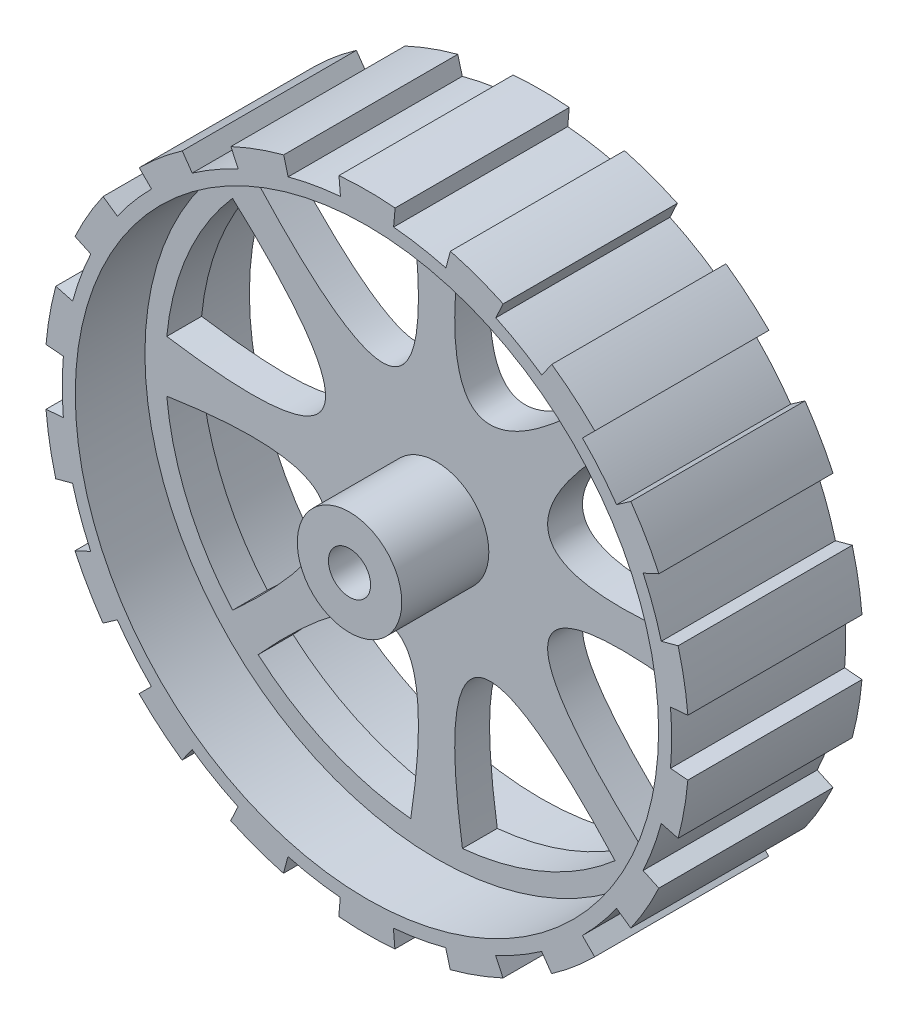
SolidWorks part; units mm, degrees
ref_plane "Front Plane" through (0, 0, 0) normal (0, 0, 1) x (1, 0, 0)
ref_plane "Top Plane" through (0, 0, 0) normal (0, 1, 0) x (1, 0, 0)
ref_plane "Right Plane" through (0, 0, 0) normal (1, 0, 0) x (0, 0, -1)
sketch "Sketch1" plane through (0, 0, 0) normal (0, 0, 1) x (1, 0, 0)
  line L0 (3.2369, 36.8581) -> (3.0619, 34.8658)
  line L1 (-3.2127, 36.8603) -> (-3.039, 34.8678)
  line L2 (15.6479, 33.5283) -> (14.8021, 31.7159)
  line L3 (9.588, 35.7361) -> (9.0698, 33.8044)
  line L4 (26.1715, 26.1544) -> (24.7569, 24.7406)
  line L5 (21.2323, 30.3017) -> (20.0846, 28.6637)
  line L6 (33.5385, 15.6259) -> (31.7256, 14.7812)
  line L7 (30.3156, 21.2124) -> (28.6769, 20.0658)
  line L8 (36.8603, 3.2127) -> (34.8678, 3.039)
  line L9 (35.7424, 9.5646) -> (33.8104, 9.0476)
  line L10 (35.7361, -9.588) -> (33.8044, -9.0698)
  line L11 (36.8581, -3.2369) -> (34.8658, -3.0619)
  line L12 (30.3017, -21.2323) -> (28.6637, -20.0846)
  line L13 (33.5283, -15.6479) -> (31.7159, -14.802)
  line L14 (21.2124, -30.3156) -> (20.0658, -28.6769)
  line L15 (26.1544, -26.1715) -> (24.7406, -24.7569)
  line L16 (9.5646, -35.7424) -> (9.0476, -33.8104)
  line L17 (15.6259, -33.5385) -> (14.7812, -31.7256)
  line L18 (-3.2369, -36.8581) -> (-3.0619, -34.8658)
  line L19 (3.2127, -36.8603) -> (3.039, -34.8678)
  line L20 (-15.6479, -33.5283) -> (-14.8021, -31.7159)
  line L21 (-9.588, -35.7361) -> (-9.0698, -33.8044)
  line L22 (-26.1715, -26.1544) -> (-24.7569, -24.7406)
  line L23 (-21.2323, -30.3017) -> (-20.0846, -28.6637)
  line L24 (-33.5385, -15.6259) -> (-31.7256, -14.7812)
  line L25 (-30.3156, -21.2124) -> (-28.6769, -20.0658)
  line L26 (-36.8603, -3.2127) -> (-34.8678, -3.039)
  line L27 (-35.7424, -9.5646) -> (-33.8104, -9.0476)
  line L28 (-35.7361, 9.588) -> (-33.8044, 9.0698)
  line L29 (-36.8581, 3.2369) -> (-34.8658, 3.0619)
  line L30 (-30.3017, 21.2323) -> (-28.6637, 20.0846)
  line L31 (-33.5283, 15.6479) -> (-31.7159, 14.802)
  line L32 (-21.2124, 30.3156) -> (-20.0658, 28.6769)
  line L33 (-26.1544, 26.1715) -> (-24.7406, 24.7569)
  line L34 (-9.5646, 35.7424) -> (-9.0476, 33.8104)
  line L35 (-15.6259, 33.5385) -> (-14.7812, 31.7256)
  line L36 (0, 33.5) -> (0, -33.5) construction
  line L37 (33.5, 0) -> (-33.5, 0) construction
  line L38 (-23.6881, -23.6881) -> (23.6881, 23.6881) construction
  line L39 (23.6881, -23.6881) -> (-23.6881, 23.6881) construction
  circle A0 centre (0, 0) radius 33.5
  arc A1 (-3.039, 34.8678) -> (-9.0476, 33.8104) centre (0, 0) ccw
  circle A2 centre (0, 0) radius 6
  arc A4 (-3.2127, 36.8603) -> (3.2369, 36.8581) centre (0, 0) cw
  arc A5 (9.588, 35.7361) -> (15.6479, 33.5283) centre (0, 0) cw
  arc A6 (21.2323, 30.3017) -> (26.1715, 26.1544) centre (0, 0) cw
  arc A7 (30.3156, 21.2124) -> (33.5385, 15.6259) centre (0, 0) cw
  arc A8 (35.7424, 9.5646) -> (36.8603, 3.2127) centre (0, 0) cw
  arc A9 (36.8581, -3.2369) -> (35.7361, -9.588) centre (0, 0) cw
  arc A10 (33.5283, -15.6479) -> (30.3017, -21.2323) centre (0, 0) cw
  arc A11 (26.1544, -26.1715) -> (21.2124, -30.3156) centre (0, 0) cw
  arc A12 (15.6259, -33.5385) -> (9.5646, -35.7424) centre (0, 0) cw
  arc A13 (3.2127, -36.8603) -> (-3.2369, -36.8581) centre (0, 0) cw
  arc A14 (-9.588, -35.7361) -> (-15.6479, -33.5283) centre (0, 0) cw
  arc A15 (-21.2323, -30.3017) -> (-26.1715, -26.1544) centre (0, 0) cw
  arc A16 (-30.3156, -21.2124) -> (-33.5385, -15.6259) centre (0, 0) cw
  arc A17 (-35.7424, -9.5646) -> (-36.8603, -3.2127) centre (0, 0) cw
  arc A18 (-36.8581, 3.2369) -> (-35.7361, 9.588) centre (0, 0) cw
  arc A19 (-33.5283, 15.6479) -> (-30.3017, 21.2323) centre (0, 0) cw
  arc A20 (-26.1544, 26.1715) -> (-21.2124, 30.3156) centre (0, 0) cw
  arc A21 (-15.6259, 33.5385) -> (-9.5646, 35.7424) centre (0, 0) cw
  arc A22 (9.0698, 33.8044) -> (3.0619, 34.8658) centre (0, 0) ccw
  arc A23 (20.0846, 28.6637) -> (14.8021, 31.7159) centre (0, 0) ccw
  arc A24 (-14.7812, 31.7256) -> (-20.0658, 28.6769) centre (0, 0) ccw
  arc A25 (-24.7406, 24.7569) -> (-28.6637, 20.0846) centre (0, 0) ccw
  arc A26 (-31.7159, 14.802) -> (-33.8044, 9.0698) centre (0, 0) ccw
  arc A27 (-34.8658, 3.0619) -> (-34.8678, -3.039) centre (0, 0) ccw
  arc A28 (-33.8104, -9.0476) -> (-31.7256, -14.7812) centre (0, 0) ccw
  arc A29 (-20.0846, -28.6637) -> (-14.8021, -31.7159) centre (0, 0) ccw
  arc A30 (-9.0698, -33.8044) -> (-3.0619, -34.8658) centre (0, 0) ccw
  arc A31 (3.039, -34.8678) -> (9.0476, -33.8104) centre (0, 0) ccw
  arc A32 (14.7812, -31.7256) -> (20.0658, -28.6769) centre (0, 0) ccw
  arc A33 (24.7406, -24.7569) -> (28.6637, -20.0846) centre (0, 0) ccw
  arc A34 (28.6769, 20.0658) -> (24.7569, 24.7406) centre (0, 0) ccw
  arc A35 (33.8104, 9.0476) -> (31.7256, 14.7812) centre (0, 0) ccw
  arc A36 (-28.6769, -20.0658) -> (-24.7569, -24.7406) centre (0, 0) ccw
  arc A37 (34.8658, -3.0619) -> (34.8678, 3.039) centre (0, 0) ccw
  arc A38 (31.7159, -14.802) -> (33.8044, -9.0698) centre (0, 0) ccw
  circle A39 centre (0, 0) radius 33.5
  arc A40 (2.9693, 30.9885) -> (20.4909, 23.4356) centre (0, 0) cw
  arc A42 (30.9885, 2.9693) -> (23.4356, 20.4909) centre (0, 0) ccw
  arc A43 (30.9885, -2.9693) -> (23.4356, -20.4909) centre (0, 0) cw
  arc A44 (2.9693, -30.9885) -> (20.4909, -23.4356) centre (0, 0) ccw
  arc A45 (-2.9693, -30.9885) -> (-20.4909, -23.4356) centre (0, 0) cw
  arc A46 (-30.9885, -2.9693) -> (-23.4356, -20.4909) centre (0, 0) ccw
  arc A47 (-30.9885, 2.9693) -> (-23.4356, 20.4909) centre (0, 0) cw
  arc A48 (-2.9693, 30.9885) -> (-20.4909, 23.4356) centre (0, 0) ccw
  circle A51 centre (0, -0.0514) radius 2.4217
  spline S0 degree 2 poles (2.9693, 30.9885) (-1.9597, -1.1944) (20.4909, 23.4356) knots 0 0 0 1 1 1
  spline S1 degree 2 poles (30.9885, 2.9693) (-1.1944, -1.9597) (23.4356, 20.4909) knots 0 0 0 1 1 1
  spline S2 degree 2 poles (30.9885, -2.9693) (-1.1944, 1.9597) (23.4356, -20.4909) knots 0 0 0 1 1 1
  spline S3 degree 2 poles (2.9693, -30.9885) (-1.9597, 1.1944) (20.4909, -23.4356) knots 0 0 0 1 1 1
  spline S4 degree 2 poles (-2.9693, -30.9885) (1.9597, 1.1944) (-20.4909, -23.4356) knots 0 0 0 1 1 1
  spline S5 degree 2 poles (-30.9885, -2.9693) (1.1944, 1.9597) (-23.4356, -20.4909) knots 0 0 0 1 1 1
  spline S6 degree 2 poles (-30.9885, 2.9693) (1.1944, -1.9597) (-23.4356, 20.4909) knots 0 0 0 1 1 1
  spline S7 degree 2 poles (-2.9693, 30.9885) (1.9597, -1.1944) (-20.4909, 23.4356) knots 0 0 0 1 1 1
  point P80 (0, 0)
  dimension "D1" = 70
  dimension "D2" = 67
  dimension "D3" = 12
  dimension "D5" = 18
  dimension "D6" = 37
extrude "Boss-Extrude1" add sketch "Sketch1" along normal blind 2 and the other way blind 2 contours A39 | S7 A48 | S0 A40 | S1 A42 | S2 A43 | S3 A44 | S4 A45 | S5 A46 | S6 A47
extrude "Boss-Extrude2" add sketch "Sketch1<3>" along normal blind 10 and the other way blind 10 separate body contours A0 | A1 L34 A21 L35 A24 L32 A20 L33 A25 L30 A19 L31 A26 L28 A18 L29 A27 L26 A17 L27 A28 L24 A16 L25 A36 L22 A15 L23 A29 L20 A14 L21 A30 L18 A13 L19 A31 L16 A12 L17 A32 L14 A11 L15 A33 L12 A10 L13 A38 L10 A9 L11 A37 L8 A8 L9 A35 L6 A7 L7 A34 L4 A6 L5 A23 L2 A5 L3 A22 L0 A4 L1
sketch "Sketch1<3>" plane through (0, 0, 0) normal (0, 0, 1) x (1, 0, 0) same geometry as "Sketch1"
extrude "Boss-Extrude3" add sketch "Sketch1<4>" along normal blind 12 and the other way blind 4 separate body contours A2
sketch "Sketch1<4>" plane through (0, 0, 0) normal (0, 0, 1) x (1, 0, 0) same geometry as "Sketch1"
sketch "Sketch4" plane through (0, 0, 12) normal (0, 0, 1) x (1, 0, 0)
extrude "Cut-Extrude1" cut sketch "Sketch1<8>" along normal blind 12 and the other way blind 4 contours A51
sketch "Sketch1<8>" plane through (0, 0, 0) normal (0, 0, 1) x (1, 0, 0) same geometry as "Sketch1"
